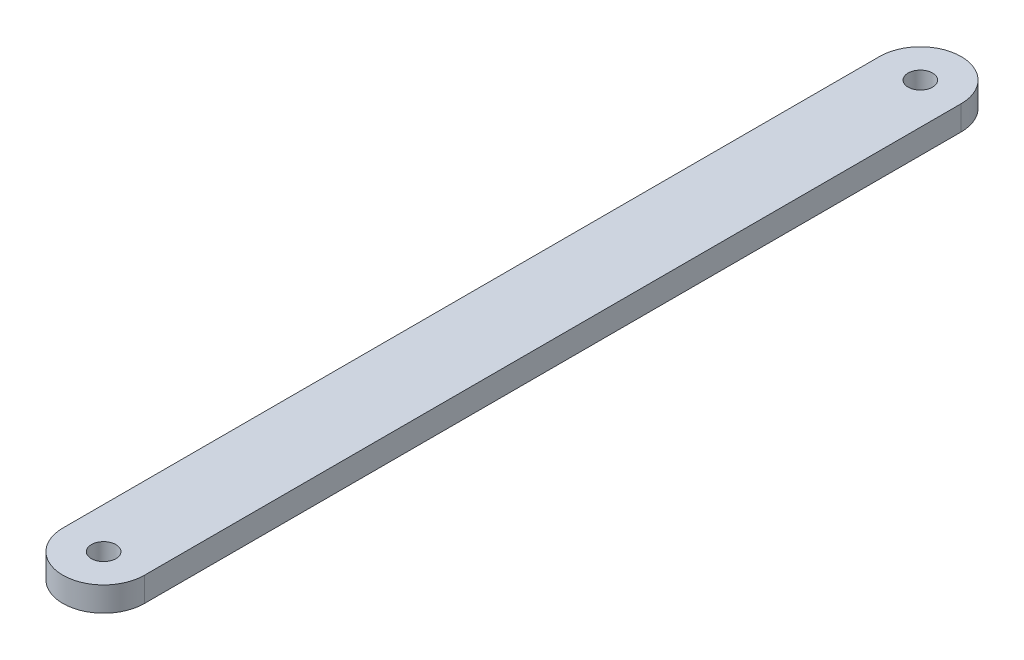
SolidWorks part; units mm, degrees
material "ABS"
ref_plane "Front Plane" through (0, 0, 0) normal (0, 0, 1) x (1, 0, 0)
ref_plane "Top Plane" through (0, 0, 0) normal (0, 1, 0) x (1, 0, 0)
ref_plane "Right Plane" through (0, 0, 0) normal (1, 0, 0) x (0, 0, -1)
sketch "Sketch2" plane through (0, 0, 0) normal (0, 0, 1) x (1, 0, 0)
  line L1 (0, 0.5) -> (-10, 0.5)
  line L2 (0, 0.5) -> (0, -2.5)
  line L3 (0, -2.5) -> (-10, -2.5)
  line L4 (-10, 0.5) -> (-10, -2.5)
  line L5 (0, 0.5) -> (-10, -2.5) construction
  line L6 (0, -2.5) -> (-10, 0.5) construction
  point P0 (-5, -1)
extrude "Boss-Extrude1" add sketch "Sketch2" along normal blind 50 and the other way blind 50
ref_plane "Plane1" through (0, 0, 50) normal (0, 0, 1) x (1, 0, 0)
sketch "Sketch3" plane through (0, 0, 50) normal (0, 0, 1) x (1, 0, 0)
  line L2 (-10, -2.5) -> (0, -2.5) construction
  line L4 (0, 0.5) -> (-5, 0.5)
  line L5 (0, 0.5) -> (0, -2.5)
  line L6 (0, -2.5) -> (-5, -2.5)
  line L7 (-5, 0.5) -> (-5, -2.5)
revolve "Revolve1" add sketch "Sketch3" angle 360 about L7 region at (-2.5, -1, 50)
mirror "Mirror1" about plane through (0, 0, 0) normal (0, 0, 1) of "Revolve1"
ref_plane "Plane2" through (0, -2.5, 0) normal (0, -1, 0) x (-1, 0, 0)
sketch "Sketch5" plane through (0, -2.5, 0) normal (0, -1, 0) x (-1, 0, 0)
  circle A0 centre (5, -50) radius 1.5
extrude "Cut-Extrude2" cut sketch "Sketch5" against normal up to surface (3 mm away) up to face at (-5, 0.5, 0)
mirror "Mirror2" about plane through (0, 0, 0) normal (0, 0, 1) of "Cut-Extrude2"
ref_plane "Plane3" through (0, -2.5, 0) normal (0, -1, 0) x (-1, 0, 0)
sketch "Sketch6" plane through (0, -2.5, 0) normal (0, -1, 0) x (-1, 0, 0)
  line L0 (10, 0) -> (0, 0)
  line L1 (10, 50) -> (10, -50) construction
